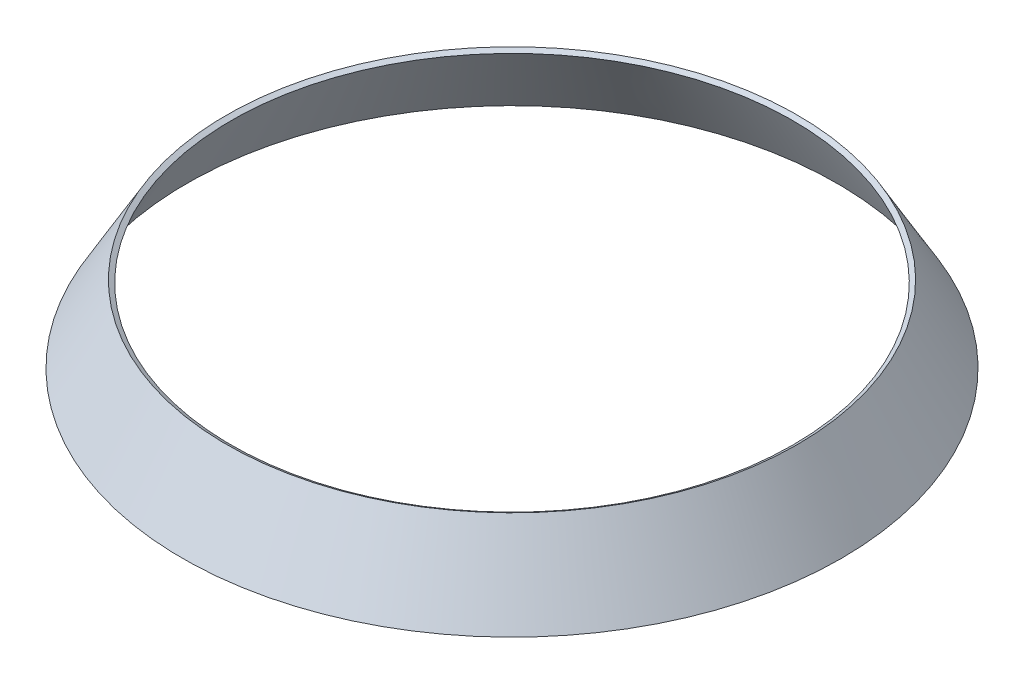
SolidWorks part; units mm, degrees
ref_plane "Front Plane" through (0, 0, 0) normal (0, 0, 1) x (1, 0, 0)
ref_plane "Top Plane" through (0, 0, 0) normal (0, 1, 0) x (1, 0, 0)
ref_plane "Right Plane" through (0, 0, 0) normal (1, 0, 0) x (0, 0, -1)
sketch "Sketch1" plane through (0, 0, 0) normal (0, 0, 1) x (1, 0, 0)
  line L0 (0, -1106.9178) -> (0, 54238.9737) construction
  line L1 (38.78, 5.3712) -> (44.78, -5.0212)
  line L2 (38.78, 5.3712) -> (38.1738, 5.0212)
  line L3 (44.78, -5.0212) -> (44.1738, -5.3712)
  line L4 (38.1738, 5.0212) -> (44.1738, -5.3712)
  line L5 (38.78, 5.3712) -> (44.1738, -5.3712) construction
  line L6 (44.78, -5.0212) -> (38.1738, 5.0212) construction
  point P1 (0, 0)
  point P4 (41.4769, 0)
  point P5 (0, 0)
  dimension "D1" = 30
  dimension "D2" = 0.7
  dimension "D3" = 44.78
  dimension "D4" = 12
revolve "Revolve1" add sketch "Sketch1" angle 360 about L0
